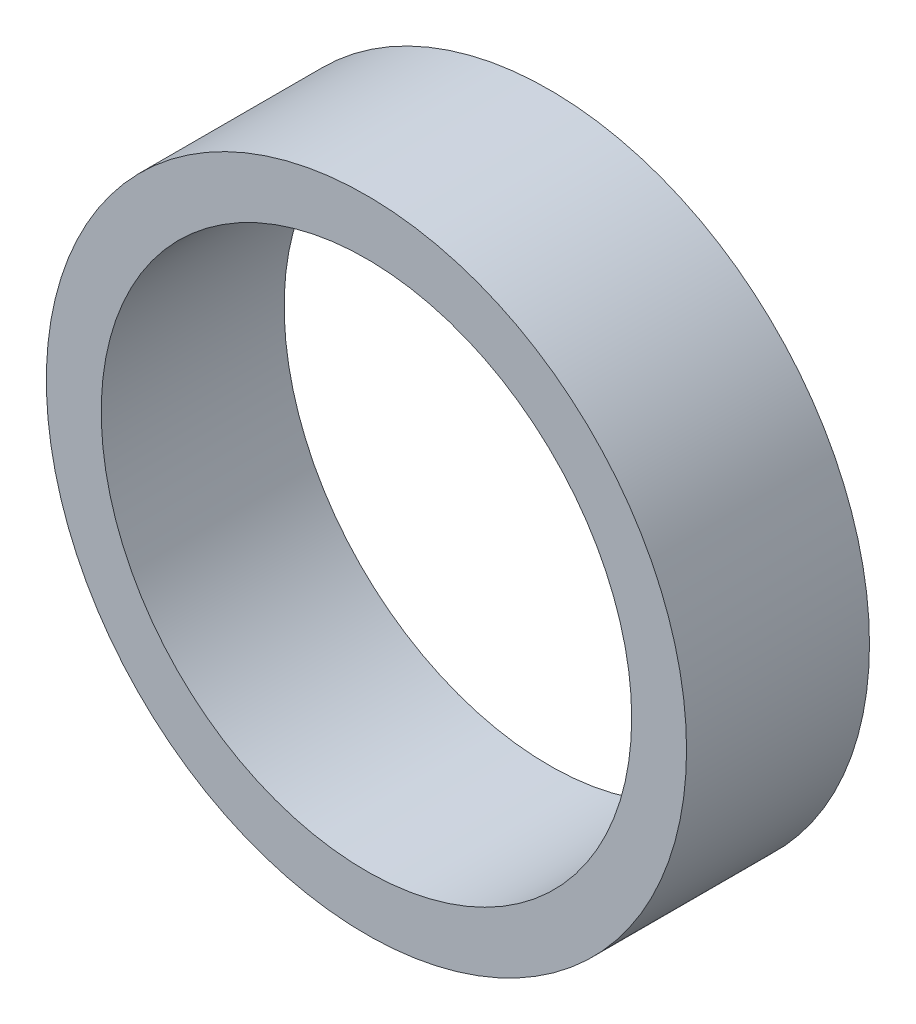
SolidWorks part; units mm, degrees
ref_plane "Plane1" through (0, 0, 0) normal (0, 0, 1) x (1, 0, 0)
ref_plane "Plane2" through (0, 0, 0) normal (0, 1, 0) x (1, 0, 0)
ref_plane "Plane3" through (0, 0, 0) normal (1, 0, 0) x (0, 0, -1)
sketch "Sketch1" plane through (0, 0, 0) normal (0, 0, 1) x (1, 0, 0)
  circle A0 centre (0, 0) radius 36.83
  circle A1 centre (0, 0) radius 44.45
extrude "BasePipeXS" add sketch "Sketch1" along normal mid plane 25.4
